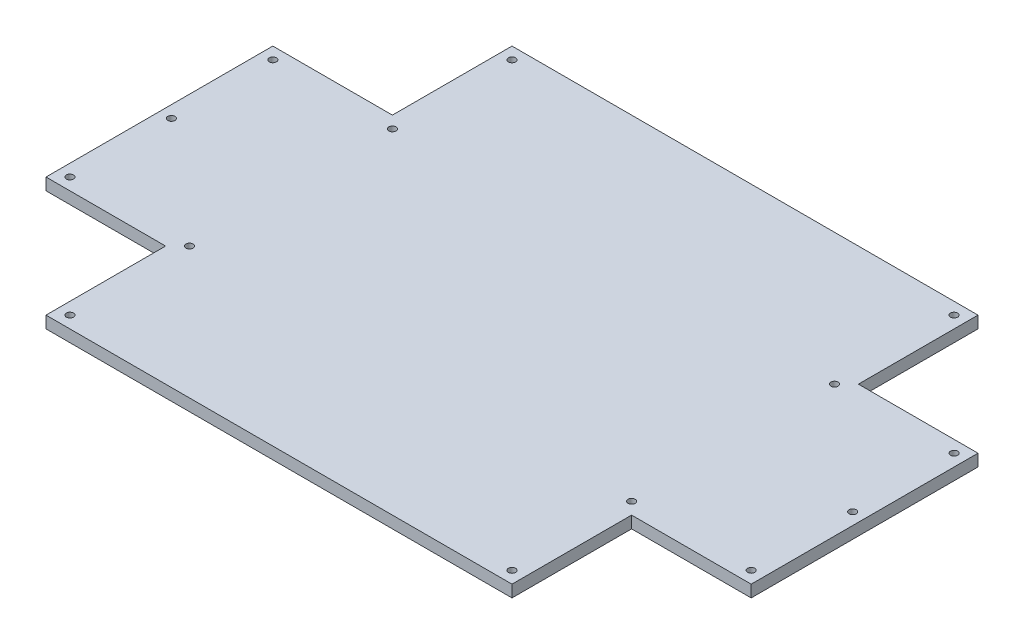
SolidWorks part; units mm, degrees
ref_plane "Plan de face" through (0, 0, 0) normal (0, 0, 1) x (1, 0, 0)
ref_plane "Plan de dessus" through (0, 0, 0) normal (0, 1, 0) x (1, 0, 0)
ref_plane "Plan de droite" through (0, 0, 0) normal (1, 0, 0) x (0, 0, -1)
sketch "Esquisse1" plane through (0, 0, 0) normal (0, 1, 0) x (1, 0, 0)
  line L0 (-147.415, 47.415) -> (-97.415, 47.415)
  line L1 (97.415, -97.415) -> (-97.415, -97.415)
  line L2 (147.415, -47.415) -> (147.415, 47.415)
  line L3 (97.415, 97.415) -> (-97.415, 97.415)
  line L4 (-147.415, -47.415) -> (-147.415, 47.415)
  line L5 (147.415, -97.415) -> (-147.415, 97.415) construction
  line L6 (147.415, 97.415) -> (-147.415, -97.415) construction
  line L7 (-97.415, 47.415) -> (-97.415, 97.415)
  line L8 (0, 97.415) -> (0, -97.415) construction
  line L9 (-147.415, 0) -> (147.415, 0) construction
  line L10 (97.415, 47.415) -> (97.415, 97.415)
  line L11 (147.415, 47.415) -> (97.415, 47.415)
  line L12 (147.415, -47.415) -> (97.415, -47.415)
  line L13 (97.415, -47.415) -> (97.415, -97.415)
  line L14 (-147.415, -47.415) -> (-97.415, -47.415)
  line L15 (-97.415, -47.415) -> (-97.415, -97.415)
  line L16 (-142.415, 47.415) -> (-142.415, -47.415) construction
  line L17 (-147.415, -42.415) -> (-92.415, -42.415) construction
  line L18 (-92.415, -42.415) -> (-92.415, -97.415) construction
  line L19 (-92.415, 42.415) -> (-92.415, 97.415) construction
  line L20 (-147.415, 42.415) -> (-92.415, 42.415) construction
  line L21 (92.415, -42.415) -> (92.415, -97.415) construction
  line L22 (147.415, -42.415) -> (92.415, -42.415) construction
  line L23 (142.415, 47.415) -> (142.415, -47.415) construction
  line L24 (147.415, 42.415) -> (92.415, 42.415) construction
  line L25 (92.415, 42.415) -> (92.415, 97.415) construction
  circle A0 centre (-92.415, 42.415) radius 1.5
  circle A1 centre (-142.415, 42.415) radius 1.5
  circle A2 centre (-142.415, 0) radius 1.5
  circle A3 centre (-142.415, -42.415) radius 1.5
  circle A4 centre (-92.415, -42.415) radius 1.5
  circle A5 centre (-92.415, -92.415) radius 1.5
  circle A6 centre (-92.415, 92.415) radius 1.5
  circle A7 centre (92.415, -92.415) radius 1.5
  circle A8 centre (92.415, -42.415) radius 1.5
  circle A9 centre (142.415, -42.415) radius 1.5
  circle A10 centre (142.415, 0) radius 1.5
  circle A11 centre (142.415, 42.415) radius 1.5
  circle A12 centre (92.415, 42.415) radius 1.5
  circle A13 centre (92.415, 92.415) radius 1.5
  point P0 (0, 0)
  dimension "D7" = 3
  dimension "D1" = 194.83
  dimension "D2" = 50
  dimension "D3" = 294.83
  dimension "D4" = 5
  dimension "D5" = 5
  dimension "D6" = 5
  dimension "D8" = 5
  dimension "D9" = 5
extrude "Boss.-Extru.1" add sketch "Esquisse1" along normal blind 5
sketch "Esquisse2" plane through (0, 5, 0) normal (0, 1, 0) x (1, 0, 0)
  circle A0 centre (0, 0) radius 2.7006
